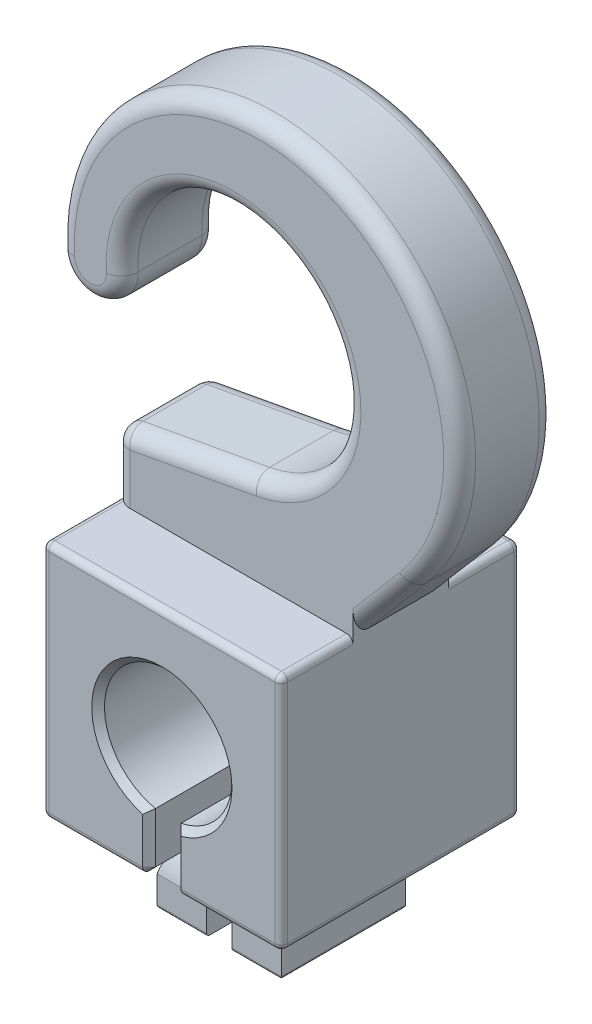
SolidWorks part; units mm, degrees
ref_plane "前视基准面" through (0, 0, 0) normal (0, 0, 1) x (1, 0, 0)
ref_plane "上视基准面" through (0, 0, 0) normal (0, 1, 0) x (1, 0, 0)
ref_plane "右视基准面" through (0, 0, 0) normal (1, 0, 0) x (0, 0, -1)
sketch "草图1" plane through (0, 0, 0) normal (0, 0, 1) x (1, 0, 0)
  line L0 (3.75, 3.75) -> (3.75, -3.75)
  line L1 (3.75, 3.75) -> (-3.75, 3.75)
  line L2 (3.75, -3.75) -> (-3.75, -3.75)
  line L3 (-3.75, 3.75) -> (-3.75, -3.75)
  line L4 (3.75, 3.75) -> (-3.75, -3.75) construction
  line L5 (3.75, -3.75) -> (-3.75, 3.75) construction
  circle A0 centre (0, 0) radius 2
  point P1 (0, 0)
  dimension "D3" = 4
  dimension "D1" = 7.5
  dimension "D2" = 7.5
extrude "凸台-拉伸1" add sketch "草图1" along normal blind 3.75 and the other way blind 3.75
sketch "草图2" plane through (0, 0, 0) normal (0, 0, 1) x (1, 0, 0)
  line L0 (0, 0) -> (0, 10) construction
  line L1 (0, 10) -> (0.8, 10) construction
  line L2 (3.75, 3.75) -> (-3.75, 3.75) construction
  line L3 (-3.75, 3.75) -> (-3.75, 5.75)
  line L4 (-3.75, 5.75) -> (0.6343, 6.558)
  line L5 (3.75, 3.75) -> (5.5938, 5.9123)
  line L6 (-3.75, 3.75) -> (3.75, 3.75)
  arc A0 (0.6343, 6.558) -> (-3.4946, 9.8056) centre (0, 10) ccw
  arc A1 (5.5938, 5.9123) -> (-5.493, 9.7028) centre (0.8, 10) ccw
  arc A2 (-5.493, 9.7028) -> (-3.4946, 9.8056) centre (-4.4936, 9.75) ccw
  dimension "D2" = 7
  dimension "D4" = 12.6
  dimension "D1" = 10
  dimension "D3" = 0.8
  dimension "D5" = 6
  dimension "D6" = 2
  dimension "D7" = 6.3
extrude "凸台-拉伸2" add sketch "草图2" along normal blind 1.5 and the other way blind 1.5
sketch "草图3" plane through (0, 0, 0) normal (0, 0, 1) x (1, 0, 0)
  line L0 (0, -3.75) -> (0, -5.75) construction
  line L1 (-3.75, -3.75) -> (3.75, -3.75) construction
  line L2 (0, -5.75) -> (0, -6.25) construction
  line L3 (-1.5, -3.75) -> (1.5, -3.75)
  line L4 (1.5, -3.75) -> (1.5, -4.4271)
  line L5 (-1.95, -6.25) -> (1.95, -6.25)
  line L6 (1.95, -6.25) -> (1.95, -5.3056)
  line L7 (-1.95, -6.25) -> (-1.95, -5.3056)
  line L8 (-1.5, -3.75) -> (-1.5, -4.4271)
  arc A0 (1.95, -5.3056) -> (1.5, -4.4271) centre (0, -5.75) ccw
  arc A1 (-1.95, -5.3056) -> (-1.5, -4.4271) centre (0, -5.75) cw
  dimension "D5" = 2
  dimension "D1" = 2
  dimension "D2" = 0.5
  dimension "D3" = 1.5
  dimension "D4" = 1.95
extrude "凸台-拉伸3" add sketch "草图3" along normal blind 2 and the other way blind 2
sketch "草图4" plane through (0, 0, 0) normal (1, 0, 0) x (0, 0, -1)
  line L0 (0, -3.75) -> (0, -5.75) construction
  line L1 (3.75, -3.75) -> (-3.75, -3.75) construction
  line L2 (0, -5.75) -> (0, -6.25) construction
  line L3 (2, -6.25) -> (-2, -6.25) construction
  line L4 (0, -3.75) -> (1.5, -3.75) construction
  line L5 (1.5, -3.75) -> (1.5, -4.4271)
  line L6 (0, -6.25) -> (1.95, -6.25) construction
  line L7 (1.95, -6.25) -> (1.95, -5.3056)
  line L8 (1.95, -6.25) -> (2, -6.25)
  line L9 (2, -6.25) -> (2, -3.75)
  line L10 (1.5, -3.75) -> (2, -3.75)
  line L12 (-1.95, -6.25) -> (-2, -6.25)
  line L13 (-1.95, -6.25) -> (-1.95, -5.3056)
  line L14 (-2, -6.25) -> (-2, -3.75)
  line L15 (-1.5, -3.75) -> (-1.5, -4.4271)
  line L16 (-2, -3.75) -> (-1.5, -3.75)
  arc A0 (1.95, -5.3056) -> (1.5, -4.4271) centre (0, -5.75) ccw
  arc A1 (-1.95, -5.3056) -> (-1.5, -4.4271) centre (0, -5.75) cw
  dimension "D4" = 2
  dimension "D1" = 2
  dimension "D2" = 1.5
  dimension "D3" = 1.95
extrude "切除-拉伸1" cut sketch "草图4" against normal blind 2 and the other way blind 2
chamfer "倒角1" distance 0.2 angle 45 2 edges at (2, 0, -3.75) (2, 0, 3.75)
fillet "圆角2" radius 0.2 10 edges at (-3.75, -3.75, 0) (3.75, -3.75, 0) (0, -3.75, 3.75) (0, -3.75, -3.75) (0, 3.75, -3.75) (0, 3.75, 3.75) (-3.75, 0, 3.75) (3.75, 0, 3.75) (3.75, 0, -3.75) (-3.75, 0, -3.75)
fillet "圆角3" radius 0.2 8 edges at (3.6914, 3.6914, -3.6914) (3.6914, 3.6914, 3.6914) (-3.6914, 3.6914, -3.6914) (-3.6914, 3.6914, 3.6914)
fillet "圆角4" radius 0.5 13 edges at (-1.5578, 6.154, 1.5) (-3.75, 5.75, 0) (2.8381, 15.9612, -1.5) (-4.4422, 8.7508, -1.5) (2.1638, 12.751, -1.5) (-1.5578, 6.154, -1.5) (2.1638, 12.751, 1.5) (-4.4422, 8.7508, 1.5) (2.8381, 15.9612, 1.5)
fillet "圆角5" radius 0.1 4 edges at (0, -6.25, 1.95) (1.95, -6.25, 0) (0, -6.25, -1.95) (-1.95, -6.25, 0)
sketch "草图5" plane through (0, 0, 0) normal (0, 0, 1) x (1, 0, 0)
  line L0 (0, 0) -> (0, -6.25) construction
  line L1 (1.85, -6.25) -> (-1.85, -6.25) construction
  line L2 (-0.4, 0) -> (-0.4, -6.25)
  line L3 (0.4, 0) -> (0.4, -6.25)
  line L4 (-0.4, 0) -> (0.4, 0)
  line L5 (-0.4, -6.25) -> (0.4, -6.25)
  dimension "D1" = 0.4
  dimension "D2" = 0.4
extrude "切除-拉伸2" cut sketch "草图5" along normal blind 3.75
chamfer "倒角2" distance 0.2 angle 45 6 edges at (0.4, -3.75, 2.525) (0.4, -3.6914, 3.6914) (0.4, -2.8567, 3.75) (-0.4, -3.75, 2.525) (-0.4, -3.6914, 3.6914) (-0.4, -2.8567, 3.75)
